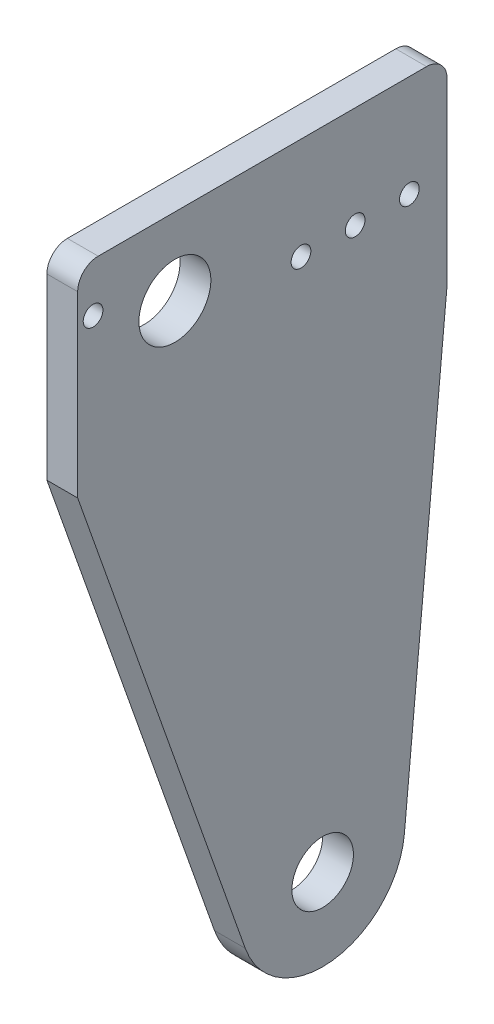
SolidWorks part; units mm, degrees
ref_plane "Front Plane" through (0, 0, 0) normal (0, 0, 1) x (1, 0, 0)
ref_plane "Top Plane" through (0, 0, 0) normal (0, 1, 0) x (1, 0, 0)
ref_plane "Right Plane" through (0, 0, 0) normal (1, 0, 0) x (0, 0, -1)
sketch "Sketch1" plane through (0, 0, 0) normal (1, 0, 0) x (0, 0, -1)
  line L0 (42.1132, 8.7376) -> (42.1132, -18.8943)
  line L1 (-15.0368, 8.7376) -> (-15.0368, -18.8943)
  line L2 (38.9382, 11.9126) -> (-11.8618, 11.9126)
  line L3 (-15.7317, -3.8354) -> (28.7183, -3.8354) construction
  line L4 (-15.0368, -18.8943) -> (10.8885, -92.1946)
  line L5 (42.1132, -18.8943) -> (35.5059, -89.149)
  line L9 (-9.4805, 9.4615) -> (-9.4805, 0) construction
  line L10 (-12.8841, 9.4615) -> (-9.4805, 9.4615) construction
  circle A0 centre (22.8617, -87.9598) radius 4.7625
  arc A1 (10.8885, -92.1946) -> (35.5059, -89.149) centre (22.8617, -87.9598) ccw
  circle A2 centre (0, 0) radius 5.5626
  circle A3 centre (-12.6555, 4.3307) radius 1.524
  arc A4 (42.1132, 8.7376) -> (38.9382, 11.9126) centre (38.9382, 8.7376) ccw
  circle A5 centre (22.8617, -87.9598) radius 77.47 construction
  circle A6 centre (36.2712, -3.8354) radius 1.524
  circle A7 centre (27.8892, -3.8354) radius 1.524
  circle A8 centre (19.5072, -3.8354) radius 1.524
  circle A9 centre (11.1252, -3.8354) radius 1.524 [skipped]
  arc A10 (-15.0368, 8.7376) -> (-11.8618, 11.9126) centre (-11.8618, 8.7376) cw
  dimension "D1" = 3.175
  dimension "D2" = 12.7
  dimension "D3" = 154.94
  dimension "D4" = 11.1252
  dimension "D6" = 3.048
  dimension "D9" = 3.048
  dimension "D13" = 5.1308
  dimension "D15" = 9.525
  dimension "D5" = 11.9126
  dimension "D8" = 5.842
  dimension "D10" = 2.3813
  dimension "D11" = 15.748
  dimension "D12" = 5.5562
  dimension "D14" = 57.15
  dimension "D7" = 3
extrude "Boss-Extrude1" add sketch "Sketch1" along normal blind 4.7625
